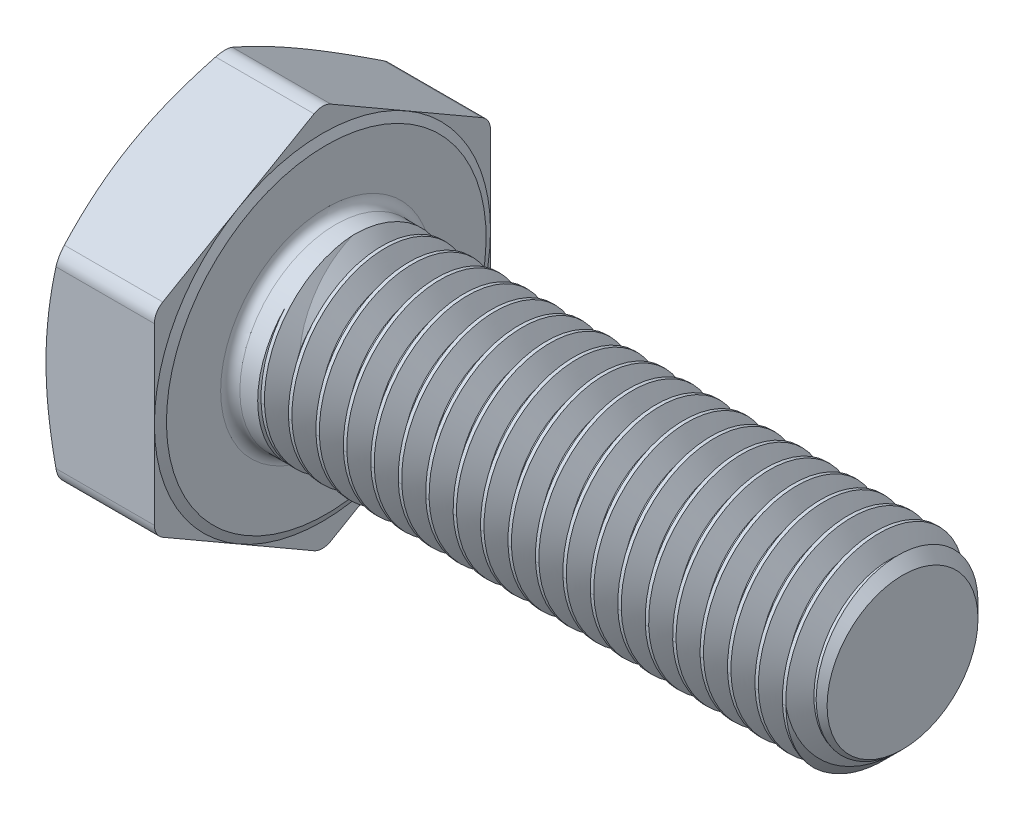
SolidWorks part; units mm, degrees
ref_plane "Front Plane" through (0, 0, 0) normal (0, 0, 1) x (1, 0, 0)
ref_plane "Top Plane" through (0, 0, 0) normal (0, 1, 0) x (1, 0, 0)
ref_plane "Right Plane" through (0, 0, 0) normal (1, 0, 0) x (0, 0, -1)
sketch "Sketch1" plane through (0, 0, 0) normal (0, 0, 1) x (1, 0, 0)
  line L0 (0, 0) -> (19.05, 0) construction
  line L1 (0, 0) -> (-3.9688, 0) construction
  line L2 (0, 5.5562) -> (0, -5.5562) construction
  line L3 (-3.9688, 5.5562) -> (-3.9687, -5.5563) construction
  line L4 (19.05, 3.175) -> (19.05, -3.175) construction
  line L8 (18.1429, 3.175) -> (19.05, 3.175) construction
  point P8 (18.1429, 0)
  point P11 (15.875, -3.175)
  point P12 (0.9071, 0)
  dimension "Head Height" = 3.9688
  dimension "Head Width" = 11.1125
  dimension "Length" = 19.05
  dimension "Thread Size" = 6.35
  dimension "D1" = 3.175
  dimension "Thread Pitch" = 0.9071
  dimension "D2" = 0.9071
sketch "Sketch2" plane through (0, 0, 0) normal (1, 0, 0) x (0, 0, -1)
  circle A0 centre (0, 0) radius 3.175
extrude "Boss-Extrude1" add sketch "Sketch2" along normal up to vertex (19.05 mm away) up to point (19.05, 3.175, 0)
sketch "Sketch3" plane through (0, 0, 0) normal (-1, 0, 0) x (0, 0, 1)
  line L0 (0, 6.4158) -> (0, 0) construction
  line L1 (0, 6.4158) -> (-5.5563, 3.2079)
  line L2 (-5.5563, 3.2079) -> (-5.5563, -3.2079)
  line L3 (-5.5563, -3.2079) -> (0, -6.4158)
  line L4 (0, -6.4158) -> (5.5562, -3.2079)
  line L5 (5.5562, -3.2079) -> (5.5562, 3.2079)
  line L6 (5.5562, 3.2079) -> (0, 6.4158)
  circle A0 centre (0, 0) radius 5.5562 construction
extrude "Boss-Extrude2" add sketch "Sketch3" along normal up to vertex (3.9688 mm away) up to point (-3.9688, 5.5562, 0)
sketch "Sketch5" plane through (-3.9688, 0, 0) normal (-1, 0, 0) x (0, 0, 1)
  circle A0 centre (0, 0) radius 5.5562 construction
  circle A1 centre (0, 0) radius 5.5562 construction
  circle A2 centre (0, 0) radius 5.0006
  dimension "D1" = 0.5556
extrude "Cut-Extrude1" cut sketch "Sketch5" against normal up to vertex (3.9688 mm away) draft 65 flip side to cut up to point (0, 0, 0)
sketch "Sketch11" plane through (-3.9688, 0, 0) normal (-1, 0, 0) x (0, 0, 1)
  line L0 (0, 3.9449) -> (0, 2.4448) construction
  line L1 (0.2223, 3.9449) -> (0.2223, 2.4448)
  line L2 (-0.2222, 3.9449) -> (-0.2222, 2.4448)
  arc A0 (0.2223, 3.9449) -> (-0.2222, 3.9449) centre (0, 3.9449) ccw
  arc A1 (-0.2222, 2.4448) -> (0.2223, 2.4448) centre (0, 2.4448) ccw
  circle A2 centre (0, 0) radius 4.1672 construction
  circle A3 centre (0, 0) radius 2.2225 construction
  point P3 (0, 3.1948)
  dimension "D1" = 8.3344
  dimension "D2" = 4.445
  dimension "D3" = 0.4445
extrude "Boss-Extrude5" add sketch "Sketch11" along normal blind 0.0635
fillet "Fillet5" radius 0.0635 4 edges at (-4.0323, 3.1948, 0.2223) (-4.0323, 2.2225, 0) (-4.0323, 3.1948, -0.2222) (-4.0323, 4.1672, 0)
pattern_circular "CirPattern1" count 6 over 360 about axis through (0, 0, 0) along (-1, 0, 0) of "Boss-Extrude5", "Fillet5" reverse direction yes
fillet "Fillet7" radius 0.5556 6 edges at (-1.6544, -6.4158, 0) (-1.6544, -3.2079, -5.5563) (-1.6544, 3.2079, -5.5563) (-1.6544, 6.4158, 0) (-1.6544, -3.2079, 5.5562) (-1.6544, 3.2079, 5.5562)
chamfer "Chamfer1" distance 0.6804 angle 45 1 edges at (19.05, 0, -3.175)
sketch "Sketch15" plane through (0, 0, 0) normal (0, 0, 1) x (1, 0, 0)
  line L0 (0, 5.2839) -> (-0.127, 5.5562)
  line L1 (0, 5.5562) -> (0, -5.5562) construction
  line L2 (-0.127, 5.5562) -> (-0.127, 6.4158)
  line L3 (-0.127, 6.4158) -> (0, 6.4158)
  line L4 (0, 6.4158) -> (0, 5.2839)
  dimension "D1" = 0.127
  dimension "D2" = 25
revolve "Cut-Revolve1" cut sketch "Sketch15" angle 360 about L1
fillet "Fillet4" radius 0.3175 1 edges at (0, 0, 3.175)
sketch "Reference Sketch1" plane through (0, 0, 0) normal (1, 0, 0) x (0, 0, -1)
  line L1 (0, 6.4158) -> (-5.5563, 3.2079)
  line L2 (-5.5563, 3.2079) -> (-5.5563, -3.2079)
  line L3 (-5.5563, -3.2079) -> (0, -6.4158)
  line L4 (0, -6.4158) -> (5.5563, -3.2079)
  line L5 (5.5563, -3.2079) -> (5.5563, 3.2079)
  line L6 (5.5563, 3.2079) -> (0, 6.4158)
  circle A0 centre (0, 0) radius 5.5563 construction
  circle A1 centre (0, 0) radius 5.5562
sketch "Sketch12" plane through (19.05, 0, 0) normal (1, 0, 0) x (0, 0, -1)
  circle A1 centre (0, 0) radius 3.175
ref_plane "Plane2" through (0.9071, 0, 0) normal (1, 0, 0) x (0, 0, -1)
split "Split1" trim tools "Plane2" bodies to split 126 116 resulting bodies 118 119
curve "Helix/Spiral2" pitch 0.9071 height 19.9571 radius 3.175 centre (19.05, 0, 0) axis (-1, 0, 0) start towards (0, 1, 0) parameters "Pitch"=0.9071
sketch "Sketch13" plane through (0, 0, 0) normal (0, 0, 1) x (1, 0, 0)
  line L0 (18.9933, 3.2732) -> (19.4469, 2.4876) construction
  line L1 (19.4469, 2.4876) -> (19.9004, 3.2732) construction
  line L2 (19.9004, 3.2732) -> (18.9933, 3.2732) construction
  line L3 (19.4469, 2.4876) -> (19.4469, 2.5858) construction
  line L4 (19.05, 3.175) -> (19.8437, 3.175)
  line L5 (19.4469, 3.175) -> (19.4469, 3.2732) construction
  line L6 (19.8437, 3.175) -> (19.5036, 2.5858)
  line L7 (19.5036, 2.5858) -> (19.3902, 2.5858)
  line L8 (19.3902, 2.5858) -> (19.05, 3.175)
  line L9 (18.1429, 3.175) -> (19.05, 3.175) construction
  dimension "D1" = 0.1134
sweep "Cut-Sweep1" cut profiles "Sketch13" path "Helix/Spiral2" align with end faces yes
sketch "Sketch14" plane through (0.9071, 0, 0) normal (1, 0, 0) x (0, 0, -1)
  circle A1 centre (0, 0) radius 3.175
  circle A2 centre (0, 0) radius 3.175
  dimension "D1" = 0
extrude "Boss-Extrude4" add sketch "Sketch14" along normal through all draft 50
equation "\"D1@Sketch11\"=\"Head Width@Sketch1\" * 0.75"
equation "\"D2@Sketch11\"=\"Head Width@Sketch1\"*0.4"
equation "\"D3@Sketch11\"=\"Head Width@Sketch1\" * .04"
equation "\"D3@Helix/Spiral2\"=\"Length@Sketch1\" + \"Thread Pitch@Sketch1\""
equation "\"D1@Chamfer1\"=\"Thread Pitch@Sketch1\"*0.750"
equation "\"D1@Sketch1\"=\"Thread Pitch@Sketch1\"*3.5"
equation "\"Pitch@Helix/Spiral2\"=\"Thread Pitch@Sketch1\""
equation "\"D1@Sketch13\"=\"Thread Pitch@Sketch1\"*0.125"
equation "\"D1@Sketch5\"=\"Head Width@Sketch1\"*0.05"
equation "\"D1@Fillet4\"=\"Thread Size@Sketch1\"*0.05"
equation "\"D2@Sketch1\"=\"Thread Pitch@Sketch1\""
equation "\"D1@Fillet7\"=\"Head Width@Sketch1\"*0.05"
